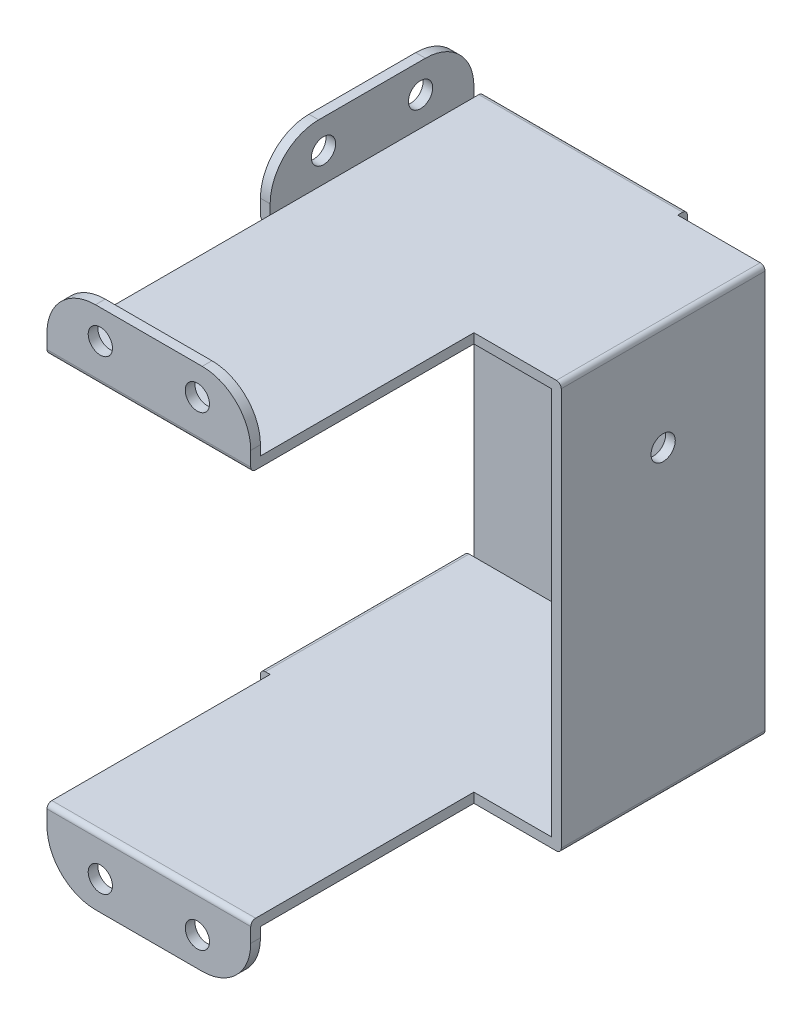
SolidWorks part; units mm, degrees
ref_plane "前视基准面" through (0, 0, 0) normal (0, 0, 1) x (1, 0, 0)
ref_plane "上视基准面" through (0, 0, 0) normal (0, 1, 0) x (1, 0, 0)
ref_plane "右视基准面" through (0, 0, 0) normal (1, 0, 0) x (0, 0, -1)
sketch "草图1" plane through (0, 0, 0) normal (0, 1, 0) x (1, 0, 0)
  line L0 (0, 0) -> (-31, 0)
  line L1 (-31, 0) -> (-31, 21)
  line L2 (-31, 21) -> (0, 21)
  line L3 (0, 21) -> (0, 0)
  dimension "D1" = 21
  dimension "D2" = 31
extrude "凸台-拉伸1" add sketch "草图1" along normal blind 42
shell "抽壳1" thickness 1 removed face at (-15.5, 21, -21) removed face at (-31, 21, -10.5) removed face at (-15.5, 21, 0)
sketch "草图2" plane through (0, 42, 0) normal (0, 1, 0) x (1, 0, 0)
  line L0 (-26, 21) -> (-26, 0)
  line L1 (0, 21) -> (-31, 21) construction
  line L2 (-31, 0) -> (0, 0) construction
  line L3 (-26, 0) -> (-31, 0)
  line L4 (-31, 0) -> (-31, 21)
  line L5 (-31, 21) -> (-26, 21)
  dimension "D1" = 5
extrude "凸台-拉伸2" add sketch "草图2" along normal blind 6
shell "抽壳2" thickness 1 removed face at (-17.8, 26.4, -21) removed face at (-17.8, 26.4, 0) removed face at (-26, 45, -10.5) removed face at (-28.5, 48, -10.5)
sketch "草图3" plane through (0, 0, 0) normal (0, -1, 0) x (1, 0, 0)
  line L0 (-31, 0) -> (-26, 0)
  line L1 (-31, 0) -> (0, 0) construction
  line L2 (-26, 0) -> (-26, -21)
  line L3 (0, -21) -> (-31, -21) construction
  line L4 (-26, -21) -> (-31, -21)
  line L5 (-31, -21) -> (-31, 0)
  dimension "D1" = 5
extrude "凸台-拉伸3" add sketch "草图3" along normal blind 6
shell "抽壳3" thickness 1 removed face at (-19.8333, 21, -21) removed face at (-28.5, -6, -10.5) removed face at (-26, -3, -10.5) removed face at (-19.8333, 21, 0)
sketch "草图4" plane through (0, 0, 0) normal (0, 0, 1) x (1, 0, 0)
  line L0 (-30, 42) -> (-30, 41)
  line L1 (-31, 41) -> (-1, 41) construction
  line L2 (-30, 41) -> (-9, 41)
  line L3 (-9, 41) -> (-9, 42)
  line L4 (-30, 42) -> (0, 42) construction
  line L5 (-9, 42) -> (-30, 42)
  line L6 (-30, 0) -> (-30, 1)
  line L7 (-31, 1) -> (-1, 1) construction
  line L8 (-30, 1) -> (-9, 1)
  line L9 (-9, 1) -> (-9, 0)
  line L10 (-30, 0) -> (0, 0) construction
  line L11 (-9, 0) -> (-30, 0)
  dimension "D1" = 21
  dimension "D2" = 21
extrude "凸台-拉伸4" add sketch "草图4" along normal blind 23
sketch "草图5" plane through (0, 42, 0) normal (0, 1, 0) x (1, 0, 0)
  line L0 (-30, -23) -> (-9, -23)
  line L1 (-9, -23) -> (-9, -18)
  line L2 (-9, -23) -> (-9, 0) construction
  line L3 (-9, -18) -> (-30, -18)
  line L4 (-30, -23) -> (-30, 0) construction
  line L5 (-30, -18) -> (-30, -23)
  dimension "D1" = 5
extrude "凸台-拉伸5" add sketch "草图5" along normal blind 6
shell "抽壳4" thickness 1 removed face at (-19.5, 45, 18) removed face at (-30, 43.6667, 13.6667) removed face at (-9, 43.6667, 13.6667) removed face at (-19.5, 48, 20.5)
sketch "草图6" plane through (0, 0, 0) normal (0, -1, 0) x (1, 0, 0)
  line L0 (-30, 23) -> (-9, 23)
  line L1 (-9, 23) -> (-9, 18)
  line L2 (-9, 23) -> (-9, 0) construction
  line L3 (-9, 18) -> (-30, 18)
  line L4 (-30, 23) -> (-30, 0) construction
  line L5 (-30, 18) -> (-30, 23)
  dimension "D1" = 5
extrude "凸台-拉伸6" add sketch "草图6" along normal blind 6
shell "抽壳5" thickness 1 removed face at (-30, -1.6667, 13.6667) removed face at (-19.5, -3, 18) removed face at (-19.5, -6, 20.5) removed face at (-9, -1.6667, 13.6667)
ref_plane "基准面1" through (-30, 42, -21) normal (-1, 0, 0) x (0, 0, 1)
sketch "草图8" plane through (0, 0, -21) normal (0, 0, -1) x (-1, 0, 0)
  line L0 (30, 42) -> (30, 0)
  line L1 (30, 39.525) -> (30, 44.475) construction
  line L2 (30, 42) -> (9, 42) construction
  line L3 (30, 0) -> (9, 0)
  line L4 (9, 0) -> (9, 42)
  line L5 (0, 42) -> (30, 42) construction
  line L6 (9, 42) -> (30, 42)
extrude "凸台-拉伸7" add sketch "草图8" along normal blind 1
hole_wizard "M3 螺纹孔1" positions "草图9" profile "草图11" tap size "M3" standard "GB" end condition up to next
sketch "草图9" plane through (0, 0, 23) normal (0, 0, 1) x (1, 0, 0)
  line L0 (-9, -6) -> (-30, -6) construction
  line L1 (-30, 48) -> (-9, 48) construction
  point P0 (-24.5, 45)
  point P2 (-14.5, 45)
  point P4 (-24.5, -3)
  point P6 (-14.5, -3)
  point P17 (-40.5406, 52.6875)
  point P18 (-19.5, 48)
  point P19 (0, 0)
  point P20 (0, 0)
  point P21 (0, 0)
  point P22 (0, 0)
  point P23 (0, 0)
  dimension "D1" = 3
  dimension "D2" = 3
  dimension "D3" = 5
  dimension "D4" = 5
sketch "草图11" plane through (-24.5, 45, 23) normal (1, 0, 0) x (0, -1, 0)
  line L0 (0, 0) -> (0, 1)
  line L1 (0, 1) -> (1.25, 1)
  line L2 (1.25, 1) -> (1.25, 0)
  line L5 (1.25, 0) -> (0, 0)
  line L11 (0, -6.35) -> (0, 107.95) construction
  dimension "通孔螺纹孔钻头直径" = 2.5
  dimension "通孔螺纹孔钻头深度" = 1
cosmetic thread "孔螺蚊线1" parameters "D2"=3
cosmetic thread "孔螺蚊线2" parameters "D2"=3
cosmetic thread "孔螺蚊线3" parameters "D2"=3
cosmetic thread "孔螺蚊线4" parameters "D2"=3
hole_wizard "M3 螺纹孔2" positions "草图12" profile "草图13" tap size "M3" standard "GB" end condition up to next
sketch "草图12" plane through (-31, 0, 0) normal (-1, 0, 0) x (0, 0, 1)
  line L0 (-21, 48) -> (0, 48) construction
  line L1 (0, -6) -> (-21, -6) construction
  point P0 (-5.5, 45)
  point P2 (-15.5, 45)
  point P4 (-15.5, -3)
  point P6 (-5.5, -3)
  point P16 (-56.9083, 45.353)
  point P19 (-10.5, -6)
  point P20 (-10.5, 48)
  point P21 (0, 0)
  point P22 (0, 0)
  point P23 (0, 0)
  dimension "D1" = 3
  dimension "D2" = 3
  dimension "D3" = 5
  dimension "D4" = 5
  dimension "D5" = 5
sketch "草图13" plane through (-31, 45, -5.5) normal (0, 1, 0) x (0, 0, 1)
  line L0 (0, 0) -> (0, 1)
  line L1 (0, 1) -> (1.25, 1)
  line L2 (1.25, 1) -> (1.25, 0)
  line L5 (1.25, 0) -> (0, 0)
  line L11 (0, -6.35) -> (0, 107.95) construction
  dimension "通孔螺纹孔钻头直径" = 2.5
  dimension "通孔螺纹孔钻头深度" = 1
cosmetic thread "孔螺蚊线5" parameters "D2"=3
cosmetic thread "孔螺蚊线6" parameters "D2"=3
cosmetic thread "孔螺蚊线7" parameters "D2"=3
cosmetic thread "孔螺蚊线8" parameters "D2"=3
hole_wizard "M3 螺纹孔3" positions "草图14" profile "草图15" tap size "M3" standard "GB" end condition up to next
sketch "草图14" plane through (0, 0, 0) normal (1, 0, 0) x (0, 0, -1)
  line L0 (0, 42) -> (21, 42) construction
  line L1 (21, 42) -> (0, 42) construction
  point P0 (10.5, 31)
  point P7 (10.5, 42)
  dimension "D1" = 11
sketch "草图15" plane through (0, 31, -10.5) normal (0, 1, 0) x (0, 0, -1)
  line L0 (0, 0) -> (0, 1)
  line L1 (0, 1) -> (1.25, 1)
  line L2 (1.25, 1) -> (1.25, 0)
  line L5 (1.25, 0) -> (0, 0)
  line L11 (0, -6.35) -> (0, 107.95) construction
  dimension "通孔螺纹孔钻头直径" = 2.5
  dimension "通孔螺纹孔钻头深度" = 1
cosmetic thread "孔螺蚊线9" parameters "D2"=3
hole_wizard "M3 螺纹孔4" positions "草图16" profile "草图17" tap size "M3" standard "GB" end condition up to next
sketch "草图16" plane through (0, 0, -22) normal (0, 0, -1) x (-1, 0, 0)
  line L0 (30, 42) -> (9, 42) construction
  point P0 (19.5, 31)
  point P5 (19.5, 42)
  dimension "D1" = 11
sketch "草图17" plane through (-19.5, 31, -22) normal (1, 0, 0) x (0, 1, 0)
  line L0 (0, 0) -> (0, 1)
  line L1 (0, 1) -> (1.25, 1)
  line L2 (1.25, 1) -> (1.25, 0)
  line L5 (1.25, 0) -> (0, 0)
  line L11 (0, -6.35) -> (0, 107.95) construction
  dimension "通孔螺纹孔钻头直径" = 2.5
  dimension "通孔螺纹孔钻头深度" = 1
cosmetic thread "孔螺蚊线10" parameters "D2"=3
fillet "圆角2" radius 0.5 8 edges at (-31, 1, -10.5) (-31, 41, -10.5) (-19.5, 1, 23) (-19.5, 41, 23) (-19.5, 0, -22) (-19.5, 42, -22) (0, 0, -10.5) (0, 42, -10.5)
fillet "圆角3" radius 5 8 edges at (-30.5, -6, -21) (-30.5, -6, 0) (-30, -6, 22.5) (-9, -6, 22.5) (-9, 48, 22.5) (-30, 48, 22.5) (-30.5, 48, -21) (-30.5, 48, 0)
